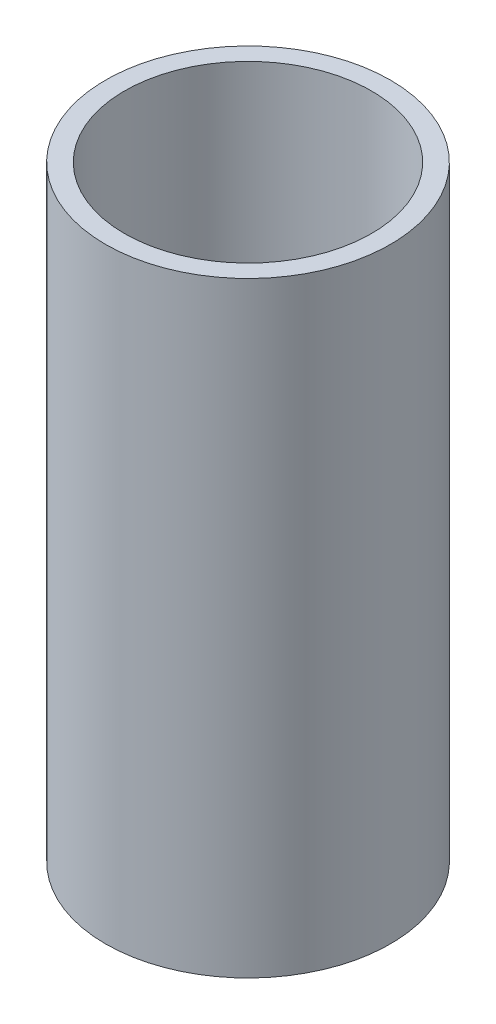
SolidWorks part; units mm, degrees
ref_plane "Front Plane" through (0, 0, 0) normal (0, 0, 1) x (1, 0, 0)
ref_plane "Top Plane" through (0, 0, 0) normal (0, 1, 0) x (1, 0, 0)
ref_plane "Right Plane" through (0, 0, 0) normal (1, 0, 0) x (0, 0, -1)
sketch "Sketch1" plane through (0, 0, 0) normal (0, 1, 0) x (1, 0, 0)
  circle A0 centre (0, 0) radius 47.5
  dimension "SLEEVE_OD" = 95
extrude "Boss-Extrude1" add sketch "Sketch1" along normal blind 202.0826
sketch "Sketch2" plane through (0, 0, 0) normal (0, 1, 0) x (1, 0, 0)
  circle A0 centre (0, 0) radius 41.2117
  dimension "BORE_D" = 82.4235
extrude "Cut-Extrude1" cut sketch "Sketch2" along normal through all
chamfer "Chamfer1" distance 2.9165 angle 60 rebuild error yes
